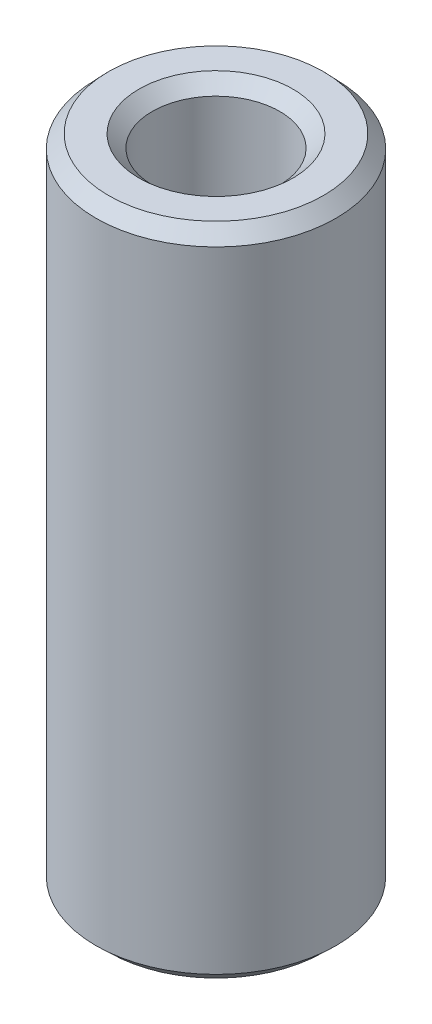
SolidWorks part; units mm, degrees
ref_plane "Front Plane" through (0, 0, 0) normal (0, 0, 1) x (1, 0, 0)
ref_plane "Top Plane" through (0, 0, 0) normal (0, 1, 0) x (1, 0, 0)
ref_plane "Right Plane" through (0, 0, 0) normal (1, 0, 0) x (0, 0, -1)
sketch "Sketch1" plane through (0, 0, 0) normal (0, 1, 0) x (1, 0, 0)
  circle A0 centre (0, 0) radius 35
  dimension "SLEEVE_OD" = 70
extrude "Boss-Extrude1" add sketch "Sketch1" along normal blind 191.2808
sketch "Sketch2" plane through (0, 0, 0) normal (0, 1, 0) x (1, 0, 0)
  circle A0 centre (0, 0) radius 18.5814
  dimension "BORE_D" = 37.1628
extrude "Cut-Extrude1" cut sketch "Sketch2" along normal through all
chamfer "Chamfer1" distance 3.8936 angle 43.4 4 edges at (0, 191.2808, 18.5814) (0, 0, 18.5814) (0, 0, 35) (0, 191.2808, 35) first distance on face at (0, 191.2808, 18.5814) first distance on face at (0, 0, 18.5814) first distance on face at (0, 191.2808, 35)
